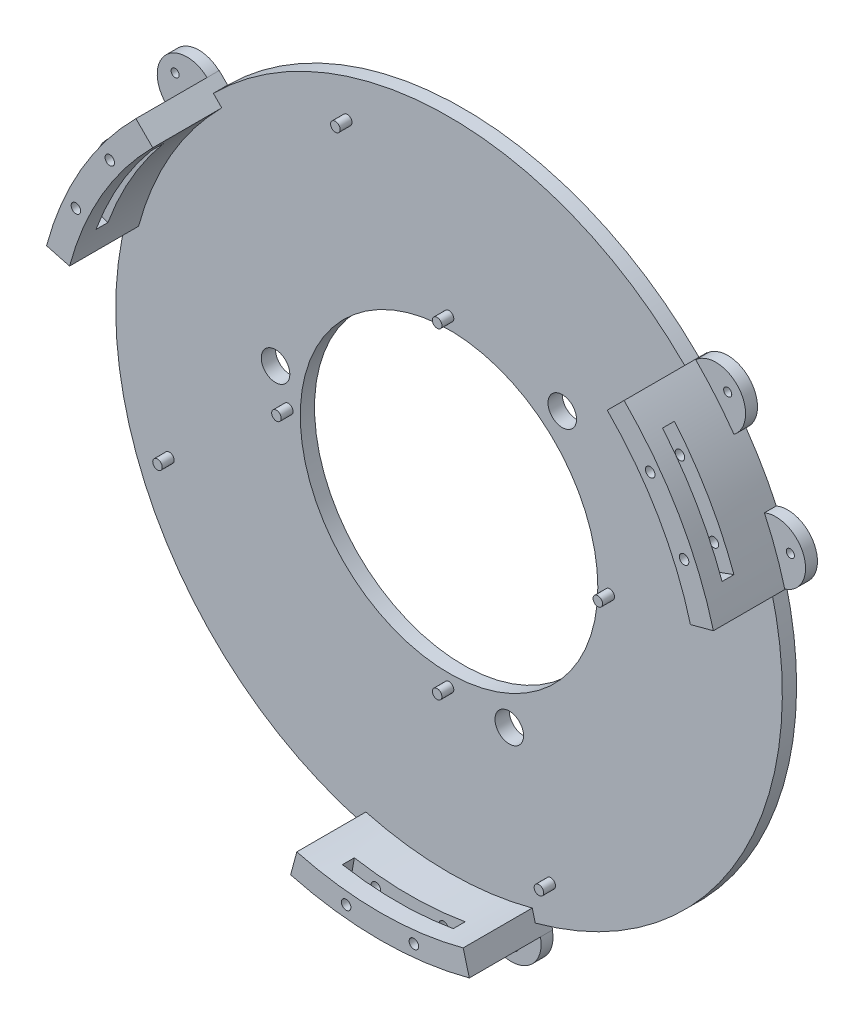
SolidWorks part; units mm, degrees
ref_plane "Piano frontale" through (0, 0, 0) normal (0, 0, 1) x (1, 0, 0)
ref_plane "Piano superiore" through (0, 0, 0) normal (0, 1, 0) x (1, 0, 0)
ref_plane "Piano destro" through (0, 0, 0) normal (1, 0, 0) x (0, 0, -1)
sketch "Schizzo1" plane through (0, 0, 0) normal (0, 0, 1) x (1, 0, 0)
  circle A0 centre (0, 0) radius 140
  dimension "D1" = 280
extrude "Estrusione-Estrusione1" add sketch "Schizzo1" along normal blind 3 and the other way blind 3
sketch "Schizzo2" plane through (0, 0, 3) normal (0, 0, 1) x (1, 0, 0)
  circle A0 centre (0, 0) radius 62.5
  dimension "D1" = 125
extrude "Taglio-Estrusione1" cut sketch "Schizzo2" against normal through all
sketch "Schizzo3" plane through (0, 0, 3) normal (0, 0, 1) x (1, 0, 0)
  circle A0 centre (0, 0) radius 67.5 construction
  circle A1 centre (0, 67.5) radius 2
  dimension "D1" = 135
extrude "Estrusione-Estrusione2" add sketch "Schizzo3" along normal blind 5
pattern_circular "RipetizioneCircolare2" count 4 every 90 about axis through (0, 0, 3) along (0, 0, 1) of "Estrusione-Estrusione2"
sketch "Schizzo4" plane through (0, 0, 3) normal (0, 0, 1) x (1, 0, 0)
  line L0 (0, 0) -> (178.542, 0) construction
  line L1 (0, 0) -> (117.4616, 42.7525) construction
  circle A0 centre (0, 0) radius 125 construction
  circle A1 centre (117.4616, 42.7525) radius 2
  dimension "D1" = 20
  dimension "D2" = 250
  dimension "D3" = 4
extrude "Estrusione-Estrusione3" add sketch "Schizzo4" along normal blind 5
pattern_circular "RipetizioneCircolare3" count 4 every 90 about axis through (0, 0, 3) along (0, 0, 1) of "Estrusione-Estrusione3"
sketch "Schizzo6" plane through (0, 0, 3) normal (0, 0, 1) x (1, 0, 0)
  line L0 (0, 0) -> (0, 140) construction
  line L1 (95.4594, 95.4594) -> (98.9949, 98.9949)
  line L2 (130.4, 34.9406) -> (135.2296, 36.2347)
  line L3 (102.5305, 102.5305) -> (98.9949, 98.9949)
  line L4 (140.0592, 37.5288) -> (135.2296, 36.2347)
  arc A0 (135.2296, 36.2347) -> (98.9949, 98.9949) centre (0, 0) ccw construction
  arc A1 (130.4, 34.9406) -> (95.4594, 95.4594) centre (0, 0) ccw
  arc A2 (140.0592, 37.5288) -> (102.5305, 102.5305) centre (0, 0) ccw
  dimension "D1" = 280
  dimension "D4" = 270
  dimension "D6" = 5
  dimension "D5" = 5
  dimension "D2" = 45
  dimension "D3" = 30
  dimension "D7" = 5
extrude "Estrusione-Estrusione5" add sketch "Schizzo6" along normal blind 35 from surface starting at face at (62.5, 0, -3)
pattern_circular "RipetizioneCircolare10" count 3 every 120 about axis through (0, 0, 3) along (0, 0, 1) of "Estrusione-Estrusione5"
ref_plane "Piano1" through (0, -140.0592, 0) normal (0, 1, 0) x (1, 0, 0)
sketch "Schizzo12" plane through (0, 0, 32) normal (0, 0, 1) x (1, 0, 0)
  line L0 (0, 0) -> (-25, -142.8286) construction
  line L1 (-25, -142.8286) -> (25, -142.8286) construction
  line L2 (25, -142.8286) -> (0, 0) construction
  line L3 (0, 0) -> (0, -39.4378) construction
  line L4 (-25, -142.8286) -> (-23.2759, -132.9783)
  line L5 (25, -142.8286) -> (23.2759, -132.9783)
  line L6 (-34.9406, -130.4) -> (-37.5288, -140.0592)
  line L7 (37.5288, -140.0592) -> (34.9406, -130.4)
  arc A0 (-37.5288, -140.0592) -> (37.5288, -140.0592) centre (0, 0) ccw construction
  arc A1 (-25, -142.8286) -> (25, -142.8286) centre (0, 0) ccw
  arc A3 (-34.9406, -130.4) -> (34.9406, -130.4) centre (0, 0) ccw
  arc A4 (-37.5288, -140.0592) -> (37.5288, -140.0592) centre (0, 0) ccw
  arc A6 (-37.5288, -140.0592) -> (37.5288, -140.0592) centre (0, 0) ccw construction
  arc A7 (-23.2759, -132.9783) -> (23.2759, -132.9783) centre (0, 0) ccw
  point P9 (0, -145)
  point P14 (0, -142.8286)
  dimension "D3" = 135
  dimension "D1" = 50
  dimension "D2" = 0
extrude "Taglio-Estrusione4" cut sketch "Schizzo12" against normal blind 5 from offset 7.5 offset against normal yes
sketch "Schizzo13" plane through (0, 0, 19.5) normal (0, 0, 1) x (1, 0, 0)
  circle A3 centre (14.2324, -139.2747) radius 2
  arc A4 (-24.1379, -137.9034) -> (24.1379, -137.9034) centre (0, 0) ccw
  arc A5 (-24.1379, -137.9034) -> (24.1379, -137.9034) centre (0, 0) ccw construction
  circle A6 centre (-14.2324, -139.2747) radius 2
  dimension "D4" = 4
  dimension "D2" = 10
  dimension "D3" = 10
  dimension "D1" = 5
extrude "Taglio-Estrusione5" cut sketch "Schizzo13" against normal blind 5 and the other way up to next
pattern_circular "RipetizioneCircolare13" count 3 over 360 about axis through (0, 0, -3) along (0, 0, 1) of "Taglio-Estrusione4", "Taglio-Estrusione5" reverse direction yes
sketch "Schizzo14" plane through (0, 0, -3) normal (0, 0, -1) x (-1, 0, 0)
  line L0 (0, 0) -> (-111.0764, 93.2042) construction
  line L1 (0, 0) -> (-136.2554, 49.5929) construction
  line L2 (0, 0) -> (-139.6469, 80.6252) construction
  line L4 (0, 0) -> (0, 37.8489) construction
  arc A0 (-102.5305, 102.5305) -> (-140.0592, 37.5288) centre (0, 0) ccw construction
  arc A4 (-102.6363, 102.4245) -> (-118.6911, 83.2912) centre (0, 0) ccw
  arc A7 (-102.6363, 102.4245) -> (-118.6911, 83.2912) centre (-111.0764, 93.2042) ccw
  arc A8 (-131.4779, 61.1439) -> (-140.0204, 37.6734) centre (-136.2554, 49.5929) ccw
  arc A9 (-131.4779, 61.1439) -> (-140.0204, 37.6734) centre (0, 0) ccw
  dimension "D1" = 10
  dimension "D2" = 25
  dimension "D3" = 60
extrude "Estrusione-Estrusione6" add sketch "Schizzo14" against normal blind 5
pattern_circular "RipetizioneCircolare14" count 3 over 360 about axis through (0, 0, 3) along (0, 0, 1) of "Estrusione-Estrusione6"
sketch "Schizzo19" plane through (0, 0, 3) normal (0, 0, 1) x (1, 0, 0)
  line L0 (-72.8758, 12.85) -> (0, 0) construction
  line L2 (0, 0) -> (47.5663, 56.6873) construction
  line L3 (0, 0) -> (25.3095, -69.5373) construction
  line L4 (0, 0) -> (0, -28.3318) construction
  circle A0 centre (0, 0) radius 74 construction
  circle A2 centre (-72.8758, 12.85) radius 6
  circle A3 centre (47.5663, 56.6873) radius 6
  circle A4 centre (25.3095, -69.5373) radius 6
  point P5 (27.194, -68.8221)
  point P7 (16.9782, -73.2785)
  point P8 (25.3095, -69.5373)
  dimension "D1" = 148
  dimension "D3" = 12
  dimension "D2" = 120
  dimension "D4" = 20
  dimension "D5" = 120
extrude "Taglio-Estrusione6" cut sketch "Schizzo19" against normal up to surface (6 mm away) up to face at (0, 0, -3)
sketch "Schizzo21" plane through (0, 0, 2) normal (0, 0, 1) x (1, 0, 0)
  line L0 (-27.3496, -155.1072) -> (-7.1418, -158.6704) construction
  line L1 (-27.3496, -155.1072) -> (-26.3077, -149.1984) construction
  line L2 (27.3496, -155.1072) -> (18.569, -156.6555) construction
  line L3 (27.3496, -155.1072) -> (26.3077, -149.1984) construction
  arc A0 (-37.3841, -140.0979) -> (-12.7868, -144.4351) centre (-25.179, -142.7971) ccw construction
  arc A1 (12.7868, -144.4351) -> (37.3841, -140.0979) centre (25.179, -142.7971) ccw construction
  dimension "D1" = 6
hole_wizard "Foro per Vite M3-2" positions "Schizzo22" profile "Schizzo23" hole size "M3" standard "ISO" end condition up to next
sketch "Schizzo22" plane through (0, 0, 2) normal (0, 0, 1) x (1, 0, 0)
  point P0 (-26.3077, -149.1984)
  point P3 (26.3077, -149.1984)
sketch "Schizzo23" plane through (-26.3077, -149.1984, 2) normal (1, 0, 0) x (0, -1, 0)
  line L0 (0, 0) -> (0, 5)
  line L1 (0, 5) -> (1.7, 5)
  line L2 (1.7, 5) -> (1.7, 0)
  line L5 (1.7, 0) -> (0, 0)
  line L11 (0, -6.35) -> (0, 107.95) construction
  dimension "Thru Hole Dia." = 3.4
  dimension "Thru Hole Depth" = 5
pattern_circular "RipetizioneCircolare17" count 3 over 360 about axis through (0, 0, 32) along (0, 0, -1) of "Foro per Vite M3-2"
